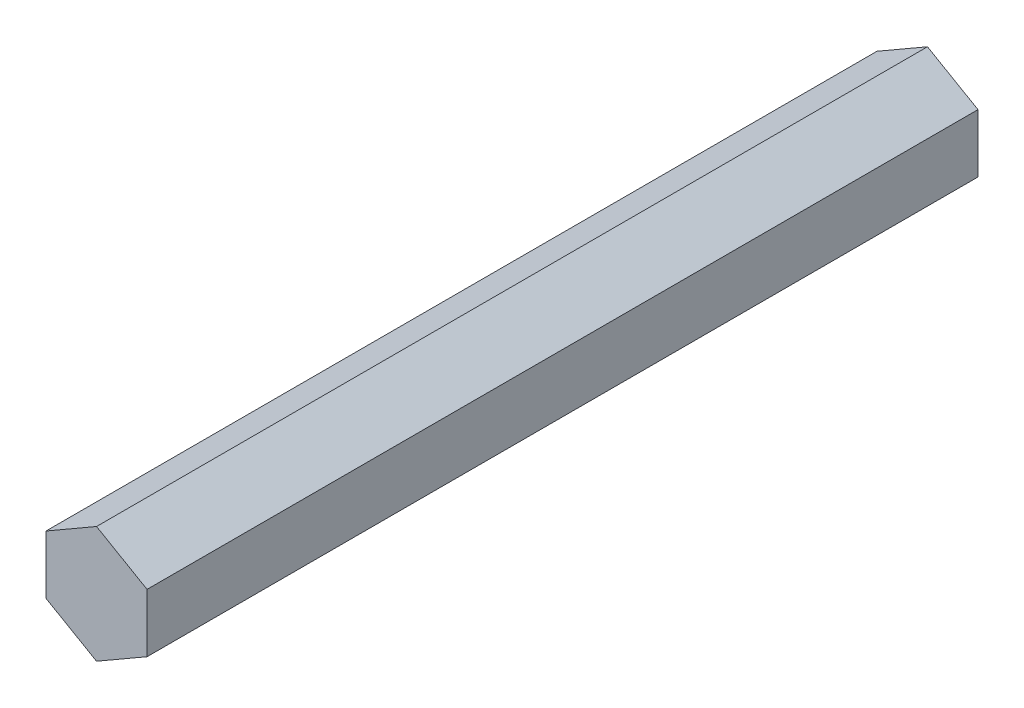
SolidWorks part; units mm, degrees
ref_plane "Front Plane" through (0, 0, 0) normal (0, 0, 1) x (1, 0, 0)
ref_plane "Top Plane" through (0, 0, 0) normal (0, 1, 0) x (1, 0, 0)
ref_plane "Right Plane" through (0, 0, 0) normal (1, 0, 0) x (0, 0, -1)
sketch "Sketch3" plane through (0, 0, 0) normal (1, 0, 0) x (0, 0, -1)
  line L0 (-18.5, 0) -> (18.5, 0) construction
  line L1 (0, 2.25) -> (0, -2.25) construction
  line L2 (-18.5, 1.5) -> (-18.5, -1.5) construction
  point P2 (12.2, 0)
  point P3 (-12.2, 0)
  dimension "Length" = 37
  dimension "Min Thread Length" = 6.3
  dimension "D1" = 6.3
  dimension "Thread Dia" = 3
  dimension "Hex" = 4.5
sketch "Sketch1" plane through (0, 0, 0) normal (0, 0, 1) x (1, 0, 0)
  line L1 (0, 2.5981) -> (-2.25, 1.299)
  line L2 (-2.25, 1.299) -> (-2.25, -1.299)
  line L3 (-2.25, -1.299) -> (0, -2.5981)
  line L4 (0, -2.5981) -> (2.25, -1.299)
  line L5 (2.25, -1.299) -> (2.25, 1.299)
  line L6 (2.25, 1.299) -> (0, 2.5981)
  circle A0 centre (0, 0) radius 2.25 construction
  circle A1 centre (0, 0) radius 1.5
extrude "Extrude1" add sketch "Sketch1" along normal up to vertex (18.5 mm away) and the other way up to vertex (18.5 mm away) contours A1 | L5 L6 L1 L2 L3 L4 A1 region at (1.0906, 1.889, 0) region at (0, 0, 0) up to point (0, 0, 18.5) other way up to point (0, 0, -18.5)
sketch "Sketch11" plane through (0, 0, -18.5) normal (0, 0, -1) x (-1, 0, 0)
  circle A0 centre (0, 0) radius 1.5 construction
  circle A1 centre (0, 0) radius 1.5
curve "Helix/Spiral1" [suppressed] pitch 0.5 height 37.5 turns 75 parameters "Pitch"=0.5
sketch "Sketch12" plane through (0, 0, 0) normal (1, 0, 0) x (0, 0, -1)
  line L0 (18.9375, 1.5) -> (18.5, 1.5)
  line L1 (18.9375, 1.5) -> (18.75, 1.1752)
  line L2 (18.75, 1.1752) -> (18.6875, 1.1752)
  line L3 (18.6875, 1.1752) -> (18.5, 1.5)
  line L4 (18.7188, 1.1752) -> (18.7188, 1.5) construction
  line L5 (18.8438, 1.3376) -> (18.5938, 1.3376) construction
  dimension "D1" = 0.0625
  dimension "D2" = 0.25
  dimension "D3" = 60
sweep "Sweep1" [suppressed] add profiles "Sketch12" path "Helix/Spiral1"
sketch "Sketch6" plane through (0, 0, -18.5) normal (0, 0, -1) x (-1, 0, 0)
  line L6 (0, 2.5981) -> (-2.25, 1.299)
  line L7 (-2.25, 1.299) -> (-2.25, -1.299)
  line L8 (-2.25, -1.299) -> (0, -2.5981)
  line L9 (0, -2.5981) -> (2.25, -1.299)
  line L10 (2.25, -1.299) -> (2.25, 1.299)
  line L11 (2.25, 1.299) -> (0, 2.5981)
  line L12 (0, 2.5981) -> (-2.25, 1.299)
  line L13 (-2.25, 1.299) -> (-2.25, -1.299)
  line L14 (-2.25, -1.299) -> (0, -2.5981)
  line L15 (0, -2.5981) -> (2.25, -1.299)
  line L16 (2.25, -1.299) -> (2.25, 1.299)
  line L17 (2.25, 1.299) -> (0, 2.5981)
  dimension "D1" = 0
extrude "Extrude2" [suppressed] cut sketch "Sketch6" along normal through all
sketch "Sketch7" plane through (0, 0, -18.5) normal (0, 0, -1) x (-1, 0, 0)
  circle A2 centre (0, 0) radius 1.5508
  circle A3 centre (0, 0) radius 1.5508
  dimension "D1" = 0.0508
extrude "Extrude3" [suppressed] cut sketch "Sketch7" against normal through all draft 43
sketch "Sketch8" plane through (0, 0, -18.5) normal (0, 0, -1) x (-1, 0, 0)
  circle A0 centre (0, 0) radius 2.25 construction
  circle A1 centre (0, 0) radius 2.25
extrude "Extrude4" [suppressed] cut sketch "Sketch8" against normal through all draft 60 flip side to cut
mirror "Mirror1" [suppressed] about plane through (0, 0, 0) normal (0, 0, 1)
sketch "Sketch9" [suppressed] plane through (0, 0, 0) normal (1, 0, 0) x (0, 0, -1)
  line L1 (-12.2, 1.5508) -> (12.2, 1.5508)
  line L2 (-12.2, 1.5508) -> (-12.2, 0)
  line L3 (-12.2, 0) -> (12.2, 0)
  line L4 (12.2, 1.5508) -> (12.2, 0)
  line L7 (-18.5, 0) -> (18.5, 0) construction
revolve "Revolve" [suppressed] add sketch "Sketch9" angle 360 about L0
sketch "Sketch10" [suppressed] plane through (0, 0, 0) normal (1, 0, 0) x (0, 0, -1)
  line L0 (18.5, 1.5) -> (12.2, 1.5)
  line L1 (-18.5, 1.5) -> (-12.2, 1.5)
  line L2 (12.2, 1.5) -> (12.2, -1.5)
  line L3 (-18.5, -1.5) -> (-12.2, -1.5)
  line L4 (-12.2, 1.5) -> (-12.2, -1.5)
  line L5 (12.2, -1.5) -> (18.5, -1.5)
ref_plane "Plane1" through (0, 0, 0) normal (0, 0, -1) x (-1, 0, 0)
ref_axis "Axis1" through (0, 0, -20.5407) along (0, 0, 1)
equation "\"D1@Sketch3\" = \"Min Thread Length@Sketch3\""
equation "\"D3@Helix/Spiral1\" = \"Length@Sketch3\"+\"Pitch@Helix/Spiral1\""
equation "\"D1@Sketch12\" = \"Pitch@Helix/Spiral1\"*.125"
equation "\"D2@Sketch12\" = \"Pitch@Helix/Spiral1\"*.5"
